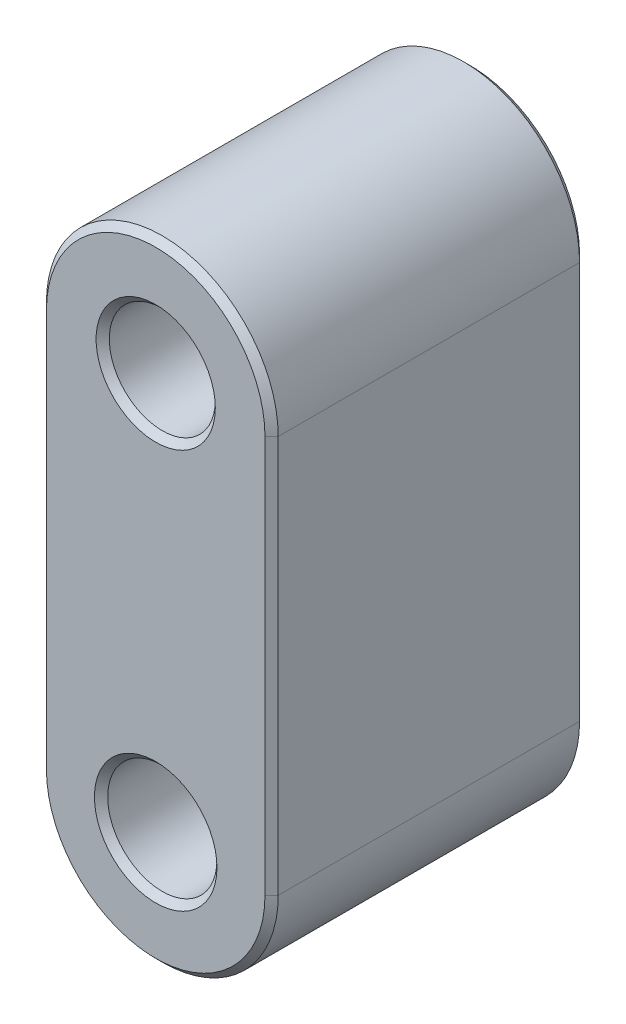
SolidWorks part; units mm, degrees
ref_plane "Front" through (0, 0, 0) normal (0, 0, 1) x (1, 0, 0)
ref_plane "Top" through (0, 0, 0) normal (0, 1, 0) x (1, 0, 0)
ref_plane "Right" through (0, 0, 0) normal (1, 0, 0) x (0, 0, -1)
sketch "Sketch1" plane through (0, 0, 0) normal (0, 0, 1) x (1, 0, 0)
  line L3 (-3.5, 0) -> (-1.6, 0) construction
  line L23 (1.65, -12) -> (3.55, -12) construction
  line L33 (-3.5, 0) -> (-3.5, -12)
  line L34 (3.5, -12) -> (3.5, 0)
  circle A0 centre (0, 0) radius 3.5 construction
  circle A3 centre (0, 0) radius 1.6
  circle A12 centre (0, -12) radius 1.65
  circle A13 centre (0, -12) radius 4.25 construction
  arc A22 (-3.5, 0) -> (3.5, 0) centre (0, 0) cw
  arc A28 (-3.5, -12) -> (3.5, -12) centre (0, -12) ccw
  dimension "D1" = 3.2
  dimension "D3" = 8.5
  dimension "D6" = 3.3
  dimension "D7" = 3.5
  dimension "D2" = 1.9
  dimension "D5" = 12
extrude "Boss-Extrude1" add sketch "Sketch1" along normal mid plane 9.5 contours A3 region at (0, -5.9711, 0)
sketch "Sketch2" plane through (0, 0, 0) normal (0, 0, 1) x (1, 0, 0)
  line L0 (-3.493, -12.2218) -> (-4.3556, 1.3622)
  line L1 (0, 0) -> (0, 8.0844) construction
  line L2 (0, 0) -> (-0.4318, 1.6114) construction
  line L3 (-0.4318, 1.6114) -> (-1.2941, 4.8296) construction
  line L4 (-1.2941, 4.8296) -> (-1.4494, 5.4092) construction
  line L5 (3.5, 1.6114) -> (3.5, -12)
  line L6 (3.5, -12) -> (3.5, 0) construction
  line L7 (3.5, -12) -> (3.5, 0) construction
  arc A0 (-4.3556, 1.3622) -> (3.5, 1.6114) centre (-0.4318, 1.6114) cw
  circle A1 centre (0, 0) radius 5 construction
  arc A2 (-3.5, -12) -> (3.5, -12) centre (0, -12) ccw construction
  dimension "D2" = 10
  dimension "D1" = 0.6
  dimension "D3" = 15
extrude "Spring" [suppressed] add sketch "Sketch2" along normal through all and the other way through all thin thin type one direction wall 1
fillet "Spring Inside Fillets" [suppressed] radius 0.25
chamfer "Deburs" [suppressed] distance 0.2 angle 45
sketch "Sketch3" [suppressed] plane through (-4.034, -0.1811, 0) normal (-0.999, -0.0448, 0) x (0, 0, 1)
  line L1 (0, -0.6807) -> (0, -9.4879) construction
  line L6 (4.55, 1.8193) -> (-4.55, 1.8193) construction
  line L8 (4.55, -11.9879) -> (-4.55, -11.9879) construction
  dimension "D1" = 2.5
  dimension "D2" = 2.5
sketch "Sketch4" [suppressed] plane through (-4.034, -0.1811, 0) normal (-0.999, -0.0448, 0) x (0, 0, 1)
  line L0 (0, -0.6807) -> (0, -9.4879)
  line L1 (-2, -2.6807) -> (0, -0.6807)
  line L2 (0, -0.6807) -> (2, -2.6807)
  line L3 (0, -0.6807) -> (0, -9.4879) construction
  line L6 (0, -12.0574) -> (0, -0.0635) construction
  dimension "D1" = 45
  dimension "D2" = 2
extrude "Arrow Point" [suppressed] add sketch "Sketch4" along normal blind 0.2 draft 55 thin contours L1 | L2 thin type one direction wall 0.8
sketch "Sketch5" [suppressed] plane through (-4.034, -0.1811, 0) normal (-0.999, -0.0448, 0) x (0, 0, 1)
  line L0 (0, -1.0846) -> (0, -9.4879)
  line L1 (0, -0.6807) -> (0, -9.4879) construction
extrude "Arrow Shaft" [suppressed] add sketch "Sketch5" along normal blind 0.2 draft 55 thin thin type mid plane wall 0.8
chamfer "Deburs no Spring" distance 0.2 angle 45 12 edges at (0, -15.5, -4.75) (3.5, -6, -4.75) (0, 3.5, -4.75) (-3.5, -6, -4.75) (1.65, -12, -4.75) (1.6, 0, -4.75) (0, 3.5, 4.75) (3.5, -6, 4.75) (0, -15.5, 4.75) (-3.5, -6, 4.75) (1.65, -12, 4.75) (1.6, 0, 4.75)
equation "\"D1@Sketch1\"=\"Clearance Hole Diameter@Box Assy.Assembly\"+.05mm"
equation "\"D6@Sketch1\"=\"Clearance Hole Diameter@Box Assy.Assembly\"+.15mm"
